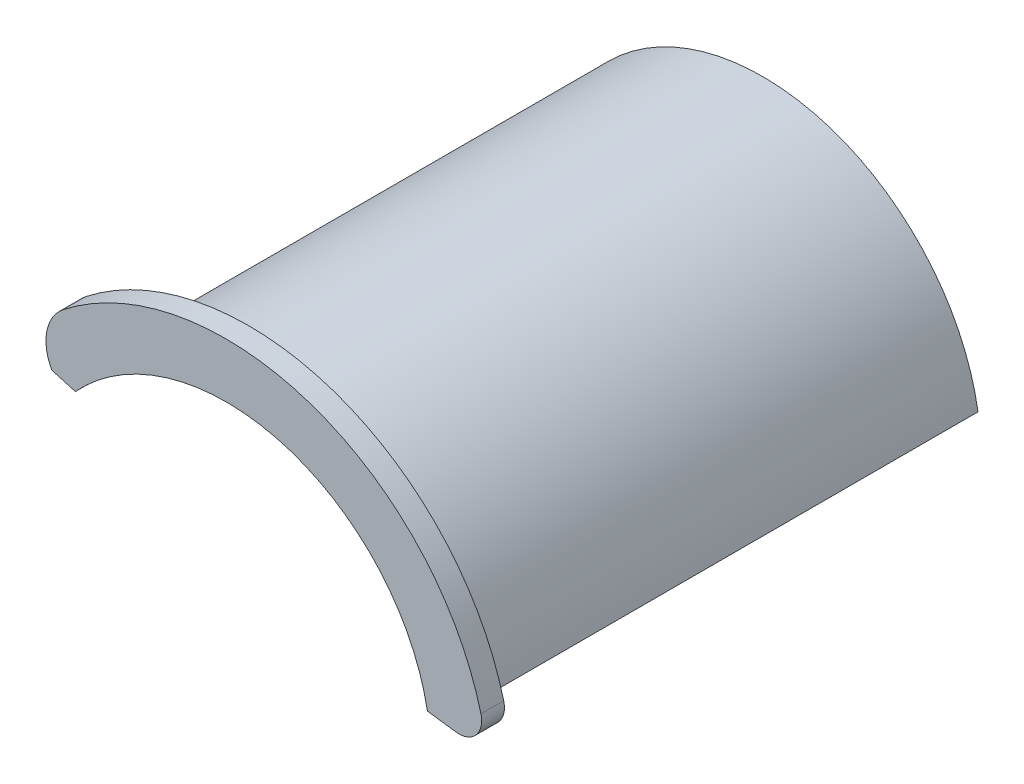
SolidWorks part; units mm, degrees
ref_plane "Plan de face" through (0, 0, 0) normal (0, 0, 1) x (1, 0, 0)
ref_plane "Plan de dessus" through (0, 0, 0) normal (0, 1, 0) x (1, 0, 0)
ref_plane "Plan de droite" through (0, 0, 0) normal (1, 0, 0) x (0, 0, -1)
sketch "Esquisse1" plane through (0, 0, 0) normal (0, 0, 1) x (1, 0, 0)
  line L0 (-48, 0) -> (-44.9982, -0.4009)
  line L1 (43.3161, -12.1949) -> (46.3179, -12.5958)
  arc A0 (43.3161, -12.1949) -> (-44.9982, -0.4009) centre (0, 0) ccw
  arc A1 (46.3179, -12.5958) -> (-48, 0) centre (0, 0) ccw
  dimension "D1" = 90
  dimension "D2" = 3
extrude "Boss.-Extru.1" add sketch "Esquisse1" along normal blind 118
sketch "Esquisse2" plane through (0, 0, 118) normal (0, 0, 1) x (1, 0, 0)
  line L0 (-44.9982, -0.4009) -> (-58.0589, 1.5119)
  line L1 (43.3161, -12.1949) -> (56.3716, -14.1794)
  line L4 (-48, 0) -> (-44.9982, -0.4009)
  line L5 (43.3161, -12.1949) -> (46.3179, -12.5958)
  line L6 (-48, 0) -> (-44.9982, -0.4009)
  line L7 (43.3161, -12.1949) -> (46.3179, -12.5958)
  arc A0 (56.3716, -14.1794) -> (-58.0589, 1.5119) centre (-0.1138, -1.0114) ccw
  arc A4 (46.3179, -12.5958) -> (-48, 0) centre (0, 0) ccw
  arc A5 (43.3161, -12.1949) -> (-44.9982, -0.4009) centre (0, 0) ccw
  arc A6 (46.3179, -12.5958) -> (-48, 0) centre (0, 0) ccw
  point P4 (0, 0)
  point P5 (0, 0)
  point P9 (0, 0)
  point P12 (0, 0)
  arc M5 (46.3179, -12.5958) -> (-48, 0) centre (0, 0) ccw
  line M8 (43.3161, -12.1949) -> (46.3179, -12.5958)
  dimension "D1" = 58
  dimension "D3" = 13.2
  dimension "D2" = 0
extrude "Boss.-Extru.2" add sketch "Esquisse2" against normal blind 5 contours L1 A0 L0 M5 M8 region at (-52.8323, 2.1214, 118)
fillet "Congé1" radius 5 1 edges at (6.373, 47.575, 113)
sketch "Esquisse4" plane through (0, 0, 0) normal (0, 0, -1) x (-1, 0, 0)
  line L0 (-44.2437, 8.2157) -> (38.3692, 31.8437)
  line L1 (-44.2437, 8.2157) -> (-114.3544, -1.1473)
  line L2 (-114.3544, -1.1473) -> (-106.5995, -56.0826)
  line L3 (-106.5995, -56.0826) -> (62.8272, -36.5668)
  line L4 (62.8272, -36.5668) -> (101.4902, -28.6149)
  line L5 (101.4902, -28.6149) -> (87.1172, 24.8584)
  line L6 (87.1172, 24.8584) -> (83.0335, 40.0517)
  line L7 (83.0335, 40.0517) -> (36.2568, 31.4555)
  arc A1 (36.2568, 31.4555) -> (36.1861, 31.2193) centre (72.1488, 20.592) ccw
  arc A2 (48, 0) -> (-46.3179, -12.5958) centre (0, 0) ccw construction
  arc M1 (48, 0) -> (-46.3179, -12.5958) centre (0, 0) ccw
  line M2 (-46.3179, -12.5958) -> (-43.3161, -12.1949)
  arc M3 (-43.3161, -12.1949) -> (44.9982, -0.4009) centre (0, 0) cw
  line M4 (44.9982, -0.4009) -> (48, 0)
extrude "Enlèv. mat.-Extru.2" cut sketch "Esquisse4" against normal through all contours L1 M3 M1 M2 | L6 L7 L0 L1 L2 L3 L4 L5 M1 M4 M3 M2 | L0 M3 M4 M1 region at (46.0663, -2.2306, 0) region at (3.3074, -12.414, 0) region at (-42.5603, 16.0301, 0)
fillet "Congé2" radius 10 1 edges at (-46.8069, 33.3943, 115.5)
fillet "Congé3" radius 5 1 edges at (57.4032, 6.4583, 115.5)
